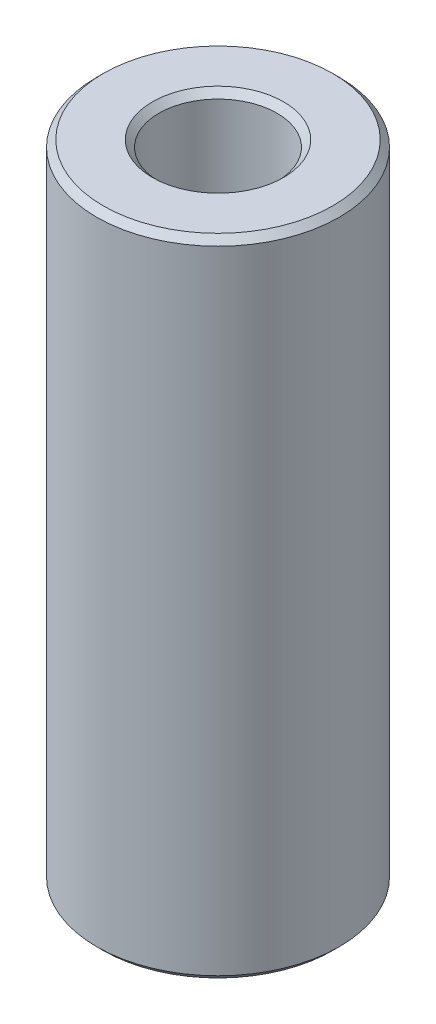
SolidWorks part; units mm, degrees
ref_plane "Front Plane" through (0, 0, 0) normal (0, 0, 1) x (1, 0, 0)
ref_plane "Top Plane" through (0, 0, 0) normal (0, 1, 0) x (1, 0, 0)
ref_plane "Right Plane" through (0, 0, 0) normal (1, 0, 0) x (0, 0, -1)
sketch "Sketch1" plane through (0, 0, 0) normal (0, 1, 0) x (1, 0, 0)
  circle A0 centre (0, 0) radius 50
  dimension "SLEEVE_OD" = 100
extrude "Boss-Extrude1" add sketch "Sketch1" along normal blind 265.8737
sketch "Sketch2" plane through (0, 0, 0) normal (0, 1, 0) x (1, 0, 0)
  circle A0 centre (0, 0) radius 24.3375
  dimension "BORE_D" = 48.675
extrude "Cut-Extrude1" cut sketch "Sketch2" along normal through all
chamfer "Chamfer1" distance 2.7054 angle 45 4 edges at (0, 265.8737, 24.3375) (0, 0, 24.3375) (0, 0, 50) (0, 265.8737, 50)
